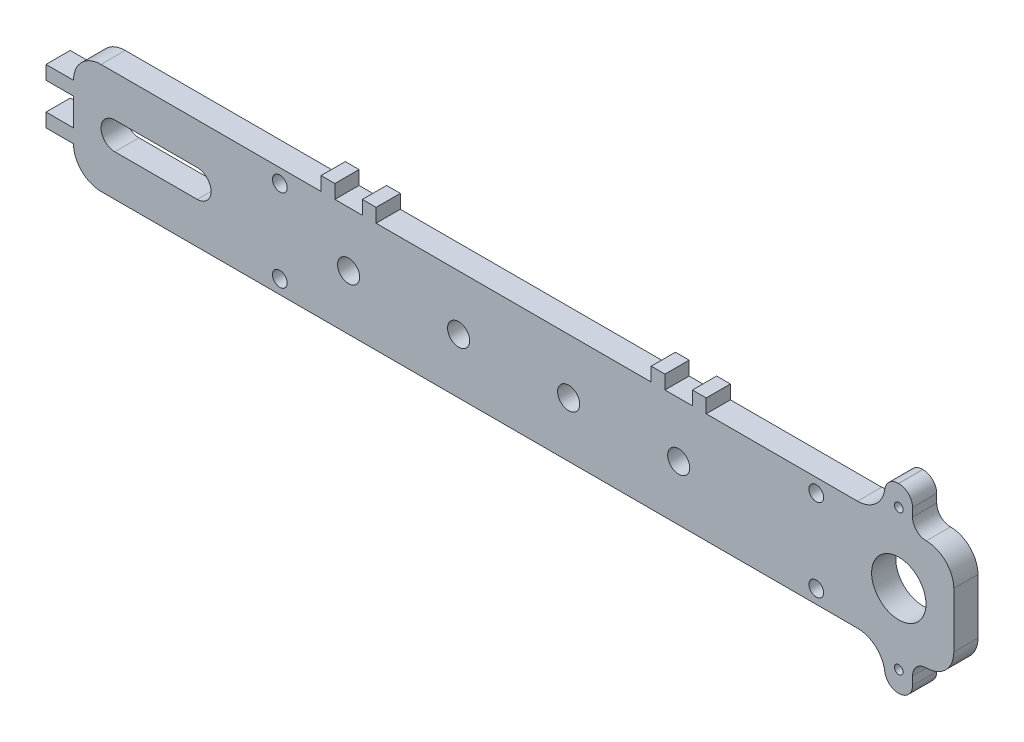
SolidWorks part; units mm, degrees
ref_plane "Front Plane" through (0, 0, 0) normal (0, 0, 1) x (1, 0, 0)
ref_plane "Top Plane" through (0, 0, 0) normal (0, 1, 0) x (1, 0, 0)
ref_plane "Right Plane" through (0, 0, 0) normal (1, 0, 0) x (0, 0, -1)
sketch "Sketch2" plane through (0, 0, 0) normal (0, 0, 1) x (1, 0, 0)
  line L0 (-101.6, 12.7) -> (-101.6, -12.7) construction
  line L1 (-101.6, 12.7) -> (101.6, 12.7) construction
  line L2 (-101.6, -12.7) -> (101.6, -12.7) construction
  line L3 (101.6, 12.7) -> (101.6, -12.7)
  line L4 (-101.6, 0) -> (101.6, 0) construction
  line L5 (-92.075, 0) -> (-73.025, 0) construction
  line L6 (-92.075, 3.175) -> (-73.025, 3.175)
  line L7 (-92.075, -3.175) -> (-73.025, -3.175)
  line L8 (88.9, -16.215) -> (88.9, 0) construction
  line L9 (88.9, 0) -> (88.9, 16.215) construction
  line L10 (92.075, 20.9775) -> (85.725, 20.9775)
  line L11 (85.725, -20.9775) -> (92.075, -20.9775)
  line L12 (85.725, 20.9775) -> (85.725, 12.7)
  line L14 (92.075, 20.9775) -> (92.075, 12.7)
  line L16 (101.6, -12.7) -> (92.075, -12.7)
  line L17 (92.075, -12.7) -> (92.075, -20.9775)
  line L18 (85.725, -20.9775) -> (85.725, -12.7)
  line L19 (85.725, -12.7) -> (-101.6, -12.7)
  line L20 (-53.975, 9.525) -> (-53.975, -9.525) construction
  line L21 (-53.975, -9.525) -> (69.85, -9.525) construction
  line L22 (69.85, -9.525) -> (69.85, 9.525) construction
  line L23 (69.85, 9.525) -> (-53.975, 9.525) construction
  line L25 (92.075, 12.7) -> (101.6, 12.7)
  line L26 (-101.6, 3.175) -> (-107.95, 3.175)
  line L27 (-107.95, 3.175) -> (-107.95, 6.35)
  line L28 (-107.95, 6.35) -> (-101.6, 6.35)
  line L29 (-101.6, -3.175) -> (-107.95, -3.175)
  line L30 (-107.95, -3.175) -> (-107.95, -6.35)
  line L31 (-107.95, -6.35) -> (-101.6, -6.35)
  line L32 (-101.6, -6.35) -> (-101.6, -12.7)
  line L33 (-101.6, 12.7) -> (-101.6, 6.35)
  line L34 (-101.6, 3.175) -> (-101.6, -3.175)
  line L35 (-41.275, 12.7) -> (-34.925, 12.7)
  line L36 (-34.925, 12.7) -> (-34.925, 15.875)
  line L37 (-34.925, 15.875) -> (-31.75, 15.875)
  line L38 (-31.75, 15.875) -> (-31.75, 12.7)
  line L39 (-41.275, 12.7) -> (-41.275, 15.875)
  line L40 (-41.275, 15.875) -> (-44.45, 15.875)
  line L41 (-44.45, 15.875) -> (-44.45, 12.7)
  line L42 (-38.1, 0) -> (-38.1, 12.7) construction
  line L43 (38.1, 0) -> (38.1, 12.7) construction
  line L44 (41.275, 12.7) -> (34.925, 12.7)
  line L45 (41.275, 12.7) -> (41.275, 15.875)
  line L46 (41.275, 15.875) -> (44.45, 15.875)
  line L47 (44.45, 15.875) -> (44.45, 12.7)
  line L48 (34.925, 12.7) -> (34.925, 15.875)
  line L49 (34.925, 15.875) -> (31.75, 15.875)
  line L50 (31.75, 15.875) -> (31.75, 12.7)
  line L51 (-44.45, 12.7) -> (-101.6, 12.7)
  line L52 (44.45, 12.7) -> (85.725, 12.7)
  line L53 (-31.75, 12.7) -> (31.75, 12.7)
  arc A0 (-92.075, 3.175) -> (-92.075, -3.175) centre (-92.075, 0) ccw
  arc A1 (-73.025, -3.175) -> (-73.025, 3.175) centre (-73.025, 0) ccw
  circle A2 centre (88.9, 0) radius 6.275
  circle A3 centre (88.9, -16.215) radius 1
  circle A4 centre (88.9, 16.215) radius 1
  circle A6 centre (12.7, 0) radius 2.5527
  circle A7 centre (38.1, 0) radius 2.5527
  circle A8 centre (-12.7, 0) radius 2.5527
  circle A9 centre (-38.1, 0) radius 2.5527
  circle A10 centre (-53.975, 9.525) radius 1.7
  circle A11 centre (-53.975, -9.525) radius 1.7
  circle A12 centre (69.85, 9.525) radius 1.7
  circle A13 centre (69.85, -9.525) radius 1.7
  point P6 (0, 0)
  point P10 (-82.55, 0)
  point P21 (88.9, 20.9775)
  point P24 (88.9, -20.9775)
  point P47 (69.85, 0)
  dimension "D2" = 12.55
  dimension "D3" = 2
  dimension "D9" = 12.7
  dimension "D16" = 5.1054
  dimension "D20" = 3.4
  dimension "D1" = 6.35
  dimension "D4" = 32.43
  dimension "D5" = 25.4
  dimension "D6" = 203.2
  dimension "D7" = 19.05
  dimension "D8" = 9.525
  dimension "D10" = 4.7625
  dimension "D11" = 6.35
  dimension "D12" = 12.7
  dimension "D13" = 12.7
  dimension "D14" = 25.4
  dimension "D15" = 25.4
  dimension "D17" = 19.05
  dimension "D18" = 19.05
  dimension "D19" = 3.175
  dimension "D21" = 3.175
  dimension "D22" = 6.35
  dimension "D23" = 3.175
extrude "Boss-Extrude1" add sketch "Sketch2" along normal blind 5.588
fillet "Fillet1" radius 6.35 6 edges at (101.6, -12.7, 2.794) (101.6, 12.7, 2.794) (-101.6, -12.7, 2.794) (-101.6, 12.7, 2.794) (85.725, -12.7, 2.794) (85.725, 12.7, 2.794)
fillet "Fillet2" radius 3.175 6 edges at (85.725, -20.9775, 2.794) (92.075, -20.9775, 2.794) (92.075, -12.7, 2.794) (92.075, 12.7, 2.794) (92.075, 20.9775, 2.794) (85.725, 20.9775, 2.794)
